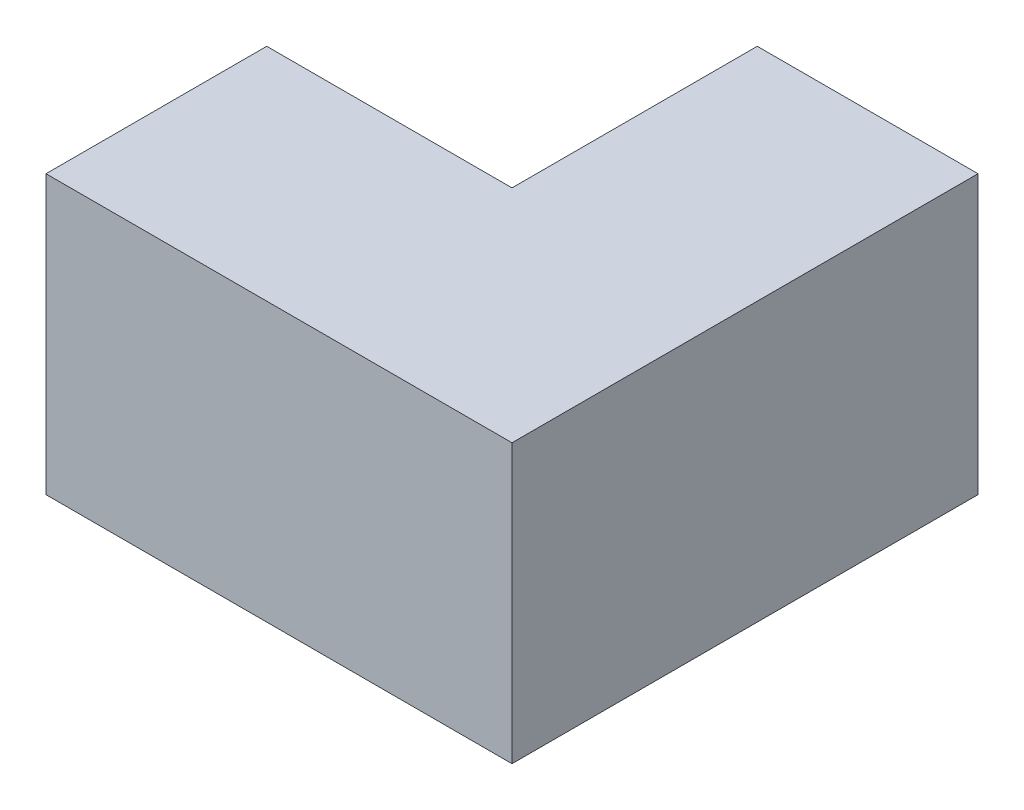
SolidWorks part; units mm, degrees
ref_plane "Front Plane" through (0, 0, 0) normal (0, 0, 1) x (1, 0, 0)
ref_plane "Top Plane" through (0, 0, 0) normal (0, 1, 0) x (1, 0, 0)
ref_plane "Right Plane" through (0, 0, 0) normal (1, 0, 0) x (0, 0, -1)
sketch "Sketch1" plane through (0, 0, 0) normal (0, 1, 0) x (1, 0, 0)
  line L0 (0, 0) -> (0, 3.5)
  line L1 (0, 3.5) -> (15, 3.5)
  line L2 (15, 3.5) -> (15, 18.5)
  line L3 (15, 18.5) -> (18.5, 18.5)
  line L4 (18.5, 18.5) -> (18.5, 0)
  line L5 (18.5, 0) -> (0, 0)
  line L6 (-5, 8.5) -> (10, 8.5)
  line L7 (10, 8.5) -> (10, 23.5)
  line L8 (10, 23.5) -> (23.5, 23.5)
  line L9 (23.5, 23.5) -> (23.5, -5)
  line L10 (23.5, -5) -> (-5, -5)
  line L11 (-5, -5) -> (-5, 8.5)
  dimension "D1" = 3.5
  dimension "D2" = 3.5
  dimension "D3" = 15
  dimension "D4" = 15
  dimension "D5" = 5
extrude "Boss-Extrude1" add sketch "Sketch1" along normal blind 15
sketch "Sketch2" plane through (0, 0, -8.5) normal (0, 0, -1) x (-1, 0, 0)
  line L0 (9.1398, 10.15) -> (-10, 10.15)
  line L1 (-10, 15) -> (5, 15) construction
  line L2 (9.1398, 6.85) -> (-10, 6.85)
  line L3 (-10, 10.15) -> (-10, 6.85)
  line L4 (-10, 15) -> (-10, 0) construction
  line L5 (9.1398, 10.15) -> (9.1398, 6.85)
  dimension "D1" = 4.85
  dimension "D2" = 3.3
extrude "Cut-Extrude1" cut sketch "Sketch2" against normal offset from surface (3 mm away) 2 up to face at (7.5, 7.5, -3.5)
chamfer "Chamfer1" distance 3 angle 45 2 edges at (2.5, 6.85, -8.5) (2.5, 10.15, -8.5)
sketch "Sketch4" plane through (0, 15, 0) normal (0, 1, 0) x (1, 0, 0)
  line L0 (-5, 8.5) -> (10, 8.5)
  line L1 (10, 8.5) -> (10, 23.5)
  line L2 (10, 23.5) -> (23.5, 23.5)
  line L3 (23.5, 23.5) -> (23.5, -5)
  line L4 (23.5, -5) -> (-5, -5)
  line L5 (-5, -5) -> (-5, 8.5)
extrude "Boss-Extrude2" add sketch "Sketch4" along normal blind 2
sketch "Sketch5" plane through (0, 0, 0) normal (0, -1, 0) x (1, 0, 0)
  line L0 (0, 0) -> (-5, 0)
  line L1 (-5, -8.5) -> (-5, 5) construction
  line L2 (-5, 0) -> (-5, -3.5)
  line L3 (-5, -3.5) -> (15, -3.5)
  line L4 (15, -3.5) -> (15, -24.3248)
  line L5 (15, -24.3248) -> (18.5, -24.3248)
  line L6 (18.5, -24.3248) -> (18.5, 0)
  line L7 (18.5, 0) -> (0, 0)
  line L8 (15, -3.5) -> (0, -3.5) construction
  line L9 (18.5, 0) -> (18.5, -18.5) construction
  line L10 (23.5, -23.5) -> (10, -23.5) construction
extrude "Cut-Extrude2" cut sketch "Sketch5" against normal up to surface (15 mm away) up to face at (11.1667, 15, -7.3333)
sketch "Sketch6" plane through (10, 0, 0) normal (-1, 0, 0) x (0, 0, 1)
  line L0 (-5.5, 10.15) -> (-5.5, 6.85)
  line L1 (-5.5, 6.85) -> (-8.5, 3.85)
  line L2 (-8.5, 3.85) -> (-8.5, 0)
  line L3 (-8.5, 0) -> (-23.5, 0)
  line L4 (-23.5, 0) -> (-23.5, 10.15)
  line L5 (-23.5, 17) -> (-23.5, 0) construction
  line L6 (-23.5, 10.15) -> (-5.5, 10.15)
extrude "Cut-Extrude3" cut sketch "Sketch6" against normal up to surface (8.5 mm away) up to face at (18.5, 7.5, -11.75)
